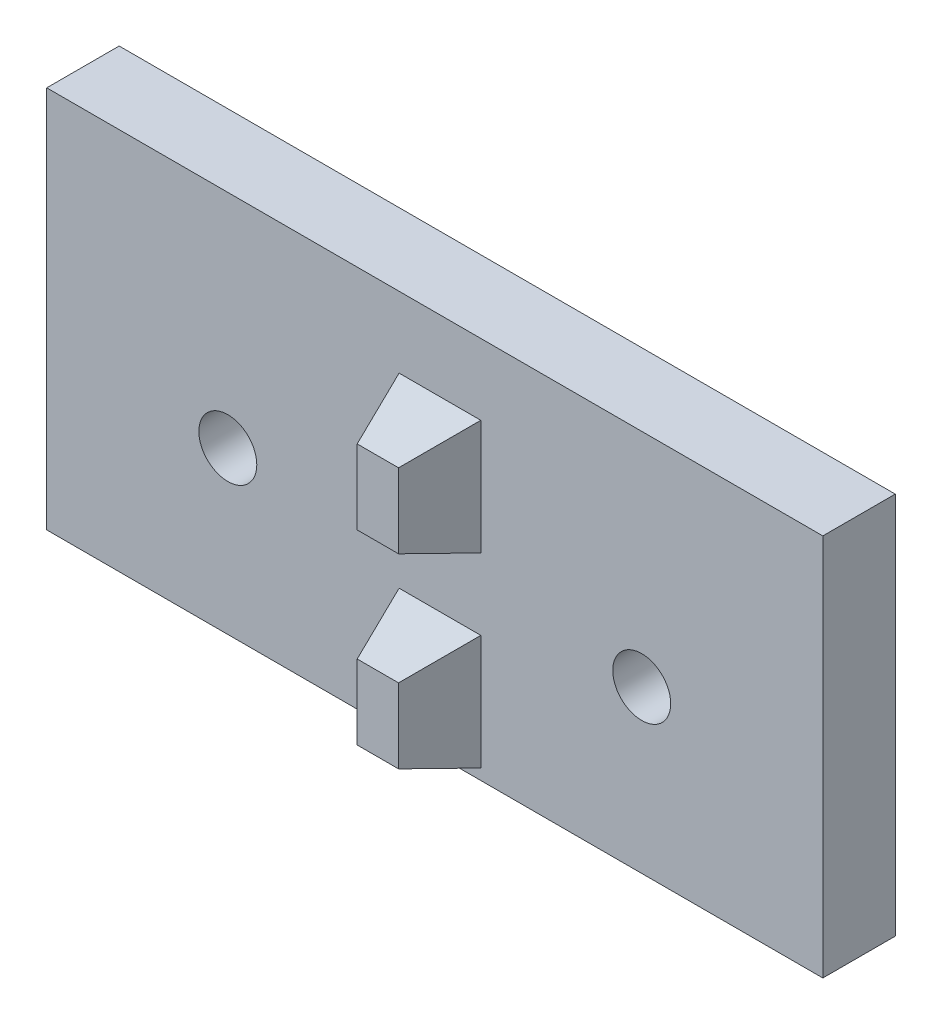
SolidWorks part; units mm, degrees
material "Настроенная пользователем пластмасса"
ref_plane "Front" through (0, 0, 0) normal (0, 0, 1) x (1, 0, 0)
ref_plane "Top" through (0, 0, 0) normal (0, 1, 0) x (1, 0, 0)
ref_plane "Right" through (0, 0, 0) normal (1, 0, 0) x (0, 0, -1)
sketch "Эскиз1" plane through (0, 0, 0) normal (0, 0, 1) x (1, 0, 0)
  line L1 (0, 0) -> (37.5, 0)
  line L2 (0, 0) -> (0, -18.5)
  line L3 (0, -18.5) -> (37.5, -18.5)
  line L4 (37.5, 0) -> (37.5, -18.5)
  circle A0 centre (8.75, -10.7) radius 1.4
  circle A1 centre (28.75, -10.7) radius 1.4
  dimension "D3" = 8.75
  dimension "D4" = 7.8
  dimension "D5" = 20
  dimension "D6" = 2.8
  dimension "D7" = 2.8
  dimension "D1" = 37.5
  dimension "D2" = 18.5
extrude "Бобышка-Вытянуть1" add sketch "Эскиз1" along normal blind 3.5
sketch "Эскиз2" plane through (0, 0, 3.5) normal (0, 0, 1) x (1, 0, 0)
  line L0 (0, 0) -> (0, -18.5) construction
  line L1 (17, -12.4) -> (21, -12.4)
  line L2 (17, -12.4) -> (17, -18)
  line L3 (17, -18) -> (21, -18)
  line L4 (21, -12.4) -> (21, -18)
  line L5 (17, -3.4) -> (21, -3.4)
  line L6 (17, -3.4) -> (17, -9)
  line L7 (17, -9) -> (21, -9)
  line L8 (21, -3.4) -> (21, -9)
  line L9 (0, -18.5) -> (37.5, -18.5) construction
  dimension "D1" = 17
  dimension "D2" = 0.5
  dimension "D3" = 5.6
  dimension "D4" = 4
  dimension "D5" = 5.6
  dimension "D6" = 4
  dimension "D7" = 3.4
  dimension "D8" = 0
extrude "Бобышка-Вытянуть2" add sketch "Эскиз2" along normal blind 3
chamfer "Фаска1" distance 1 angle 72 8 edges at (19, -3.4, 6.5) (21, -6.2, 6.5) (19, -9, 6.5) (17, -6.2, 6.5) (19, -12.4, 6.5) (21, -15.2, 6.5) (19, -18, 6.5) (17, -15.2, 6.5) first distance on face at (19, -6.2, 6.5) first distance on face at (19, -15.2, 6.5)
